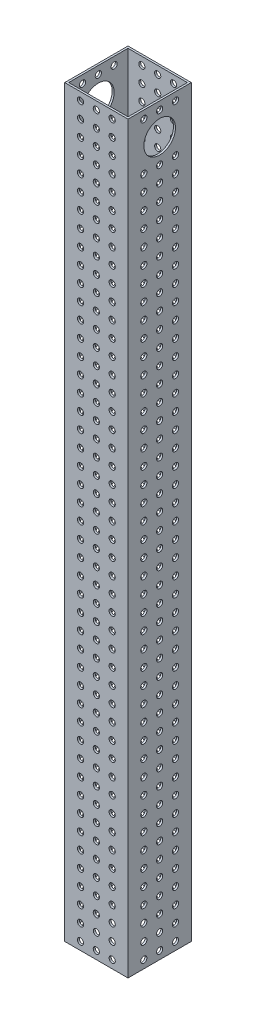
SolidWorks part; units mm, degrees
ref_plane "Front Plane" through (0, 0, 0) normal (0, 0, 1) x (1, 0, 0)
ref_plane "Top Plane" through (0, 0, 0) normal (0, 1, 0) x (1, 0, 0)
ref_plane "Right Plane" through (0, 0, 0) normal (1, 0, 0) x (0, 0, -1)
sketch "Sketch1" plane through (0, 0, 0) normal (0, 1, 0) x (1, 0, 0)
  line L1 (-25.4, 25.4) -> (25.4, 25.4)
  line L2 (-25.4, 25.4) -> (-25.4, -25.4)
  line L3 (-25.4, -25.4) -> (25.4, -25.4)
  line L4 (25.4, 25.4) -> (25.4, -25.4)
  line L5 (-25.4, 25.4) -> (25.4, -25.4) construction
  line L6 (-25.4, -25.4) -> (25.4, 25.4) construction
  line L7 (23.8125, 23.8125) -> (-23.8125, 23.8125)
  line L8 (23.8125, 23.8125) -> (23.8125, -23.8125)
  line L9 (23.8125, -23.8125) -> (-23.8125, -23.8125)
  line L10 (-23.8125, 23.8125) -> (-23.8125, -23.8125)
  line L11 (23.8125, 23.8125) -> (-23.8125, -23.8125) construction
  line L12 (23.8125, -23.8125) -> (-23.8125, 23.8125) construction
  point P0 (0, 0)
  point P6 (0, 0)
  dimension "D1" = 50.8
  dimension "D2" = 50.8
  dimension "D3" = 1.5875
  dimension "D4" = 1.5875
extrude "Boss-Extrude1" add sketch "Sketch1" along normal blind 685.8
sketch "Sketch2" plane through (0, 0, 25.4) normal (0, 0, 1) x (1, 0, 0)
  line L0 (0, 685.8) -> (0, 0) construction
  line L1 (-25.4, 685.8) -> (25.4, 685.8) construction
  line L2 (-25.4, 685.8) -> (-25.4, 0) construction
  line L3 (-6.35, 685.8) -> (-6.35, 0) construction
  line L5 (-25.4, 0) -> (25.4, 0) construction
  circle A0 centre (-12.7, 679.45) radius 2.4892
  circle A1 centre (-12.7, 666.75) radius 2.4892
  circle A2 centre (-12.7, 654.05) radius 2.4892
  circle A3 centre (-12.7, 641.35) radius 2.4892
  circle A4 centre (-12.7, 628.65) radius 2.4892
  circle A5 centre (-12.7, 615.95) radius 2.4892
  circle A6 centre (-12.7, 603.25) radius 2.4892
  circle A7 centre (-12.7, 590.55) radius 2.4892
  circle A8 centre (-12.7, 577.85) radius 2.4892
  circle A9 centre (-12.7, 565.15) radius 2.4892
  circle A10 centre (-12.7, 552.45) radius 2.4892
  circle A11 centre (-12.7, 539.75) radius 2.4892
  circle A12 centre (-12.7, 527.05) radius 2.4892
  circle A13 centre (-12.7, 514.35) radius 2.4892
  circle A14 centre (-12.7, 501.65) radius 2.4892
  circle A15 centre (-12.7, 488.95) radius 2.4892
  circle A16 centre (-12.7, 476.25) radius 2.4892
  circle A17 centre (-12.7, 463.55) radius 2.4892
  circle A18 centre (-12.7, 450.85) radius 2.4892
  circle A19 centre (-12.7, 438.15) radius 2.4892
  circle A20 centre (-12.7, 425.45) radius 2.4892
  circle A21 centre (-12.7, 412.75) radius 2.4892
  circle A22 centre (-12.7, 400.05) radius 2.4892
  circle A23 centre (-12.7, 387.35) radius 2.4892
  circle A24 centre (-12.7, 374.65) radius 2.4892
  circle A25 centre (-12.7, 361.95) radius 2.4892
  circle A26 centre (-12.7, 349.25) radius 2.4892
  circle A27 centre (-12.7, 336.55) radius 2.4892
  circle A28 centre (-12.7, 323.85) radius 2.4892
  circle A29 centre (-12.7, 311.15) radius 2.4892
  circle A30 centre (-12.7, 298.45) radius 2.4892
  circle A31 centre (-12.7, 285.75) radius 2.4892
  circle A32 centre (-12.7, 273.05) radius 2.4892
  circle A33 centre (-12.7, 260.35) radius 2.4892
  circle A34 centre (-12.7, 247.65) radius 2.4892
  circle A35 centre (-12.7, 234.95) radius 2.4892
  circle A36 centre (-12.7, 222.25) radius 2.4892
  circle A37 centre (-12.7, 209.55) radius 2.4892
  circle A38 centre (-12.7, 196.85) radius 2.4892
  circle A39 centre (-12.7, 184.15) radius 2.4892
  circle A40 centre (-12.7, 171.45) radius 2.4892
  circle A41 centre (-12.7, 158.75) radius 2.4892
  circle A42 centre (-12.7, 146.05) radius 2.4892
  circle A43 centre (-12.7, 133.35) radius 2.4892
  circle A44 centre (-12.7, 120.65) radius 2.4892
  circle A45 centre (-12.7, 107.95) radius 2.4892
  circle A46 centre (-12.7, 95.25) radius 2.4892
  circle A47 centre (-12.7, 82.55) radius 2.4892
  circle A48 centre (-12.7, 69.85) radius 2.4892
  circle A49 centre (-12.7, 57.15) radius 2.4892
  circle A50 centre (-12.7, 44.45) radius 2.4892
  circle A51 centre (-12.7, 31.75) radius 2.4892
  circle A52 centre (-12.7, 19.05) radius 2.4892
  circle A53 centre (-12.7, 6.35) radius 2.4892
  circle A54 centre (12.7, 6.35) radius 2.4892
  circle A55 centre (12.7, 19.05) radius 2.4892
  circle A56 centre (12.7, 31.75) radius 2.4892
  circle A57 centre (12.7, 44.45) radius 2.4892
  circle A58 centre (12.7, 57.15) radius 2.4892
  circle A59 centre (12.7, 69.85) radius 2.4892
  circle A60 centre (12.7, 82.55) radius 2.4892
  circle A61 centre (12.7, 95.25) radius 2.4892
  circle A62 centre (12.7, 107.95) radius 2.4892
  circle A63 centre (12.7, 120.65) radius 2.4892
  circle A64 centre (12.7, 133.35) radius 2.4892
  circle A65 centre (12.7, 146.05) radius 2.4892
  circle A66 centre (12.7, 158.75) radius 2.4892
  circle A67 centre (12.7, 171.45) radius 2.4892
  circle A68 centre (12.7, 184.15) radius 2.4892
  circle A69 centre (12.7, 196.85) radius 2.4892
  circle A70 centre (12.7, 209.55) radius 2.4892
  circle A71 centre (12.7, 222.25) radius 2.4892
  circle A72 centre (12.7, 234.95) radius 2.4892
  circle A73 centre (12.7, 247.65) radius 2.4892
  circle A74 centre (12.7, 260.35) radius 2.4892
  circle A75 centre (12.7, 273.05) radius 2.4892
  circle A76 centre (12.7, 285.75) radius 2.4892
  circle A77 centre (12.7, 298.45) radius 2.4892
  circle A78 centre (12.7, 311.15) radius 2.4892
  circle A79 centre (12.7, 323.85) radius 2.4892
  circle A80 centre (12.7, 336.55) radius 2.4892
  circle A81 centre (12.7, 374.65) radius 2.4892
  circle A82 centre (12.7, 361.95) radius 2.4892
  circle A83 centre (12.7, 349.25) radius 2.4892
  circle A84 centre (12.7, 387.35) radius 2.4892
  circle A85 centre (12.7, 400.05) radius 2.4892
  circle A86 centre (12.7, 412.75) radius 2.4892
  circle A87 centre (12.7, 425.45) radius 2.4892
  circle A88 centre (12.7, 438.15) radius 2.4892
  circle A89 centre (12.7, 450.85) radius 2.4892
  circle A90 centre (12.7, 463.55) radius 2.4892
  circle A91 centre (12.7, 476.25) radius 2.4892
  circle A92 centre (12.7, 488.95) radius 2.4892
  circle A93 centre (12.7, 501.65) radius 2.4892
  circle A94 centre (12.7, 514.35) radius 2.4892
  circle A95 centre (12.7, 527.05) radius 2.4892
  circle A96 centre (12.7, 539.75) radius 2.4892
  circle A97 centre (12.7, 552.45) radius 2.4892
  circle A98 centre (12.7, 565.15) radius 2.4892
  circle A99 centre (12.7, 577.85) radius 2.4892
  circle A100 centre (12.7, 590.55) radius 2.4892
  circle A101 centre (12.7, 603.25) radius 2.4892
  circle A102 centre (12.7, 615.95) radius 2.4892
  circle A103 centre (12.7, 628.65) radius 2.4892
  circle A104 centre (12.7, 641.35) radius 2.4892
  circle A105 centre (12.7, 654.05) radius 2.4892
  circle A106 centre (12.7, 666.75) radius 2.4892
  circle A107 centre (12.7, 679.45) radius 2.4892
  circle A108 centre (0, 6.35) radius 2.4892
  circle A109 centre (0, 19.05) radius 2.4892
  circle A110 centre (0, 31.75) radius 2.4892
  circle A111 centre (0, 44.45) radius 2.4892
  circle A112 centre (0, 57.15) radius 2.4892
  circle A113 centre (0, 69.85) radius 2.4892
  circle A114 centre (0, 82.55) radius 2.4892
  circle A115 centre (0, 95.25) radius 2.4892
  circle A116 centre (0, 107.95) radius 2.4892
  circle A117 centre (0, 120.65) radius 2.4892
  circle A118 centre (0, 133.35) radius 2.4892
  circle A119 centre (0, 146.05) radius 2.4892
  circle A120 centre (0, 158.75) radius 2.4892
  circle A121 centre (0, 171.45) radius 2.4892
  circle A122 centre (0, 184.15) radius 2.4892
  circle A123 centre (0, 196.85) radius 2.4892
  circle A124 centre (0, 209.55) radius 2.4892
  circle A125 centre (0, 222.25) radius 2.4892
  circle A126 centre (0, 234.95) radius 2.4892
  circle A127 centre (0, 247.65) radius 2.4892
  circle A128 centre (0, 260.35) radius 2.4892
  circle A129 centre (0, 273.05) radius 2.4892
  circle A130 centre (0, 285.75) radius 2.4892
  circle A131 centre (0, 298.45) radius 2.4892
  circle A132 centre (0, 311.15) radius 2.4892
  circle A133 centre (0, 323.85) radius 2.4892
  circle A134 centre (0, 336.55) radius 2.4892
  circle A135 centre (0, 349.25) radius 2.4892
  circle A136 centre (0, 361.95) radius 2.4892
  circle A137 centre (0, 374.65) radius 2.4892
  circle A138 centre (0, 387.35) radius 2.4892
  circle A139 centre (0, 400.05) radius 2.4892
  circle A140 centre (0, 412.75) radius 2.4892
  circle A141 centre (0, 425.45) radius 2.4892
  circle A142 centre (0, 438.15) radius 2.4892
  circle A143 centre (0, 450.85) radius 2.4892
  circle A144 centre (0, 463.55) radius 2.4892
  circle A145 centre (0, 476.25) radius 2.4892
  circle A146 centre (0, 488.95) radius 2.4892
  circle A147 centre (0, 501.65) radius 2.4892
  circle A148 centre (0, 514.35) radius 2.4892
  circle A149 centre (0, 527.05) radius 2.4892
  circle A150 centre (0, 539.75) radius 2.4892
  circle A151 centre (0, 552.45) radius 2.4892
  circle A152 centre (0, 565.15) radius 2.4892
  circle A153 centre (0, 577.85) radius 2.4892
  circle A154 centre (0, 590.55) radius 2.4892
  circle A155 centre (0, 603.25) radius 2.4892
  circle A156 centre (0, 615.95) radius 2.4892
  circle A157 centre (0, 628.65) radius 2.4892
  circle A158 centre (0, 641.35) radius 2.4892
  circle A159 centre (0, 654.05) radius 2.4892
  circle A160 centre (0, 666.75) radius 2.4892
  circle A161 centre (0, 679.45) radius 2.4892
  dimension "D1" = 4.9784
  dimension "D2" = 6.35
  dimension "D3" = 12.7
  dimension "D5" = 12.7
  dimension "D6" = 6.35
  dimension "D4" = 54
extrude "Cut-Extrude1" cut sketch "Sketch2" against normal through all
sketch "Sketch4" plane through (25.4, 0, 0) normal (1, 0, 0) x (0, 0, -1)
  line L0 (0, 685.8) -> (0, 0) construction
  line L1 (-25.4, 685.8) -> (25.4, 685.8) construction
  line L2 (-25.4, 685.8) -> (-25.4, 0) construction
  line L3 (-6.35, -314.2) -> (-6.35, 49685.8) construction
  line L4 (25.4, 584.2) -> (-25.4, 584.2) construction
  line L5 (25.4, 685.8) -> (25.4, 0) construction
  circle A0 centre (-12.7, 679.45) radius 2.4892
  circle A1 centre (-12.7, 666.75) radius 2.4892
  circle A2 centre (-12.7, 654.05) radius 2.4892
  circle A3 centre (-12.7, 641.35) radius 2.4892
  circle A4 centre (-12.7, 628.65) radius 2.4892
  circle A5 centre (-12.7, 615.95) radius 2.4892
  circle A6 centre (-12.7, 603.25) radius 2.4892
  circle A7 centre (-12.7, 590.55) radius 2.4892
  circle A10 centre (-12.7, 552.45) radius 2.4892
  circle A11 centre (-12.7, 539.75) radius 2.4892
  circle A12 centre (-12.7, 527.05) radius 2.4892
  circle A13 centre (-12.7, 514.35) radius 2.4892
  circle A14 centre (-12.7, 501.65) radius 2.4892
  circle A15 centre (-12.7, 488.95) radius 2.4892
  circle A16 centre (-12.7, 476.25) radius 2.4892
  circle A17 centre (-12.7, 463.55) radius 2.4892
  circle A18 centre (-12.7, 450.85) radius 2.4892
  circle A19 centre (-12.7, 438.15) radius 2.4892
  circle A20 centre (-12.7, 425.45) radius 2.4892
  circle A21 centre (-12.7, 412.75) radius 2.4892
  circle A22 centre (-12.7, 400.05) radius 2.4892
  circle A23 centre (-12.7, 387.35) radius 2.4892
  circle A24 centre (-12.7, 374.65) radius 2.4892
  circle A25 centre (-12.7, 361.95) radius 2.4892
  circle A26 centre (-12.7, 349.25) radius 2.4892
  circle A27 centre (-12.7, 336.55) radius 2.4892
  circle A28 centre (-12.7, 323.85) radius 2.4892
  circle A29 centre (-12.7, 311.15) radius 2.4892
  circle A30 centre (-12.7, 298.45) radius 2.4892
  circle A31 centre (-12.7, 285.75) radius 2.4892
  circle A32 centre (-12.7, 273.05) radius 2.4892
  circle A33 centre (-12.7, 260.35) radius 2.4892
  circle A34 centre (-12.7, 247.65) radius 2.4892
  circle A35 centre (-12.7, 234.95) radius 2.4892
  circle A36 centre (-12.7, 222.25) radius 2.4892
  circle A37 centre (-12.7, 209.55) radius 2.4892
  circle A38 centre (-12.7, 196.85) radius 2.4892
  circle A39 centre (-12.7, 184.15) radius 2.4892
  circle A40 centre (-12.7, 171.45) radius 2.4892
  circle A41 centre (-12.7, 158.75) radius 2.4892
  circle A42 centre (-12.7, 146.05) radius 2.4892
  circle A43 centre (-12.7, 133.35) radius 2.4892
  circle A44 centre (-12.7, 120.65) radius 2.4892
  circle A45 centre (-12.7, 107.95) radius 2.4892
  circle A46 centre (-12.7, 95.25) radius 2.4892
  circle A47 centre (-12.7, 82.55) radius 2.4892
  circle A48 centre (-12.7, 69.85) radius 2.4892
  circle A49 centre (-12.7, 57.15) radius 2.4892
  circle A50 centre (-12.7, 44.45) radius 2.4892
  circle A51 centre (-12.7, 31.75) radius 2.4892
  circle A52 centre (-12.7, 19.05) radius 2.4892
  circle A53 centre (-12.7, 6.35) radius 2.4892
  circle A54 centre (12.7, 273.05) radius 2.4892
  circle A55 centre (12.7, 285.75) radius 2.4892
  circle A56 centre (12.7, 298.45) radius 2.4892
  circle A57 centre (12.7, 311.15) radius 2.4892
  circle A58 centre (12.7, 323.85) radius 2.4892
  circle A59 centre (12.7, 336.55) radius 2.4892
  circle A60 centre (12.7, 349.25) radius 2.4892
  circle A61 centre (12.7, 361.95) radius 2.4892
  circle A62 centre (12.7, 374.65) radius 2.4892
  circle A63 centre (12.7, 387.35) radius 2.4892
  circle A64 centre (12.7, 400.05) radius 2.4892
  circle A65 centre (12.7, 412.75) radius 2.4892
  circle A66 centre (12.7, 425.45) radius 2.4892
  circle A67 centre (12.7, 438.15) radius 2.4892
  circle A68 centre (12.7, 450.85) radius 2.4892
  circle A69 centre (12.7, 463.55) radius 2.4892
  circle A70 centre (12.7, 476.25) radius 2.4892
  circle A71 centre (12.7, 488.95) radius 2.4892
  circle A72 centre (12.7, 501.65) radius 2.4892
  circle A73 centre (12.7, 514.35) radius 2.4892
  circle A74 centre (12.7, 527.05) radius 2.4892
  circle A75 centre (12.7, 539.75) radius 2.4892
  circle A76 centre (12.7, 552.45) radius 2.4892
  circle A79 centre (12.7, 590.55) radius 2.4892
  circle A80 centre (12.7, 603.25) radius 2.4892
  circle A81 centre (12.7, 615.95) radius 2.4892
  circle A82 centre (12.7, 628.65) radius 2.4892
  circle A83 centre (12.7, 641.35) radius 2.4892
  circle A84 centre (12.7, 654.05) radius 2.4892
  circle A85 centre (12.7, 666.75) radius 2.4892
  circle A86 centre (12.7, 19.05) radius 2.4892
  circle A87 centre (12.7, 31.75) radius 2.4892
  circle A88 centre (12.7, 44.45) radius 2.4892
  circle A89 centre (12.7, 57.15) radius 2.4892
  circle A90 centre (12.7, 69.85) radius 2.4892
  circle A91 centre (12.7, 82.55) radius 2.4892
  circle A92 centre (12.7, 95.25) radius 2.4892
  circle A93 centre (12.7, 107.95) radius 2.4892
  circle A94 centre (12.7, 120.65) radius 2.4892
  circle A95 centre (12.7, 133.35) radius 2.4892
  circle A96 centre (12.7, 146.05) radius 2.4892
  circle A97 centre (12.7, 158.75) radius 2.4892
  circle A98 centre (12.7, 171.45) radius 2.4892
  circle A99 centre (12.7, 184.15) radius 2.4892
  circle A100 centre (12.7, 196.85) radius 2.4892
  circle A101 centre (12.7, 209.55) radius 2.4892
  circle A102 centre (12.7, 222.25) radius 2.4892
  circle A103 centre (12.7, 234.95) radius 2.4892
  circle A104 centre (12.7, 247.65) radius 2.4892
  circle A105 centre (12.7, 260.35) radius 2.4892
  circle A106 centre (12.7, 6.35) radius 2.4892
  circle A107 centre (12.7, 679.45) radius 2.4892
  circle A108 centre (0, 6.35) radius 2.4892
  circle A109 centre (0, 19.05) radius 2.4892
  circle A110 centre (0, 31.75) radius 2.4892
  circle A111 centre (0, 44.45) radius 2.4892
  circle A112 centre (0, 57.15) radius 2.4892
  circle A113 centre (0, 69.85) radius 2.4892
  circle A114 centre (0, 82.55) radius 2.4892
  circle A115 centre (0, 95.25) radius 2.4892
  circle A116 centre (0, 107.95) radius 2.4892
  circle A117 centre (0, 120.65) radius 2.4892
  circle A118 centre (0, 133.35) radius 2.4892
  circle A119 centre (0, 146.05) radius 2.4892
  circle A120 centre (0, 158.75) radius 2.4892
  circle A121 centre (0, 171.45) radius 2.4892
  circle A122 centre (0, 184.15) radius 2.4892
  circle A123 centre (0, 196.85) radius 2.4892
  circle A124 centre (0, 209.55) radius 2.4892
  circle A125 centre (0, 222.25) radius 2.4892
  circle A126 centre (0, 234.95) radius 2.4892
  circle A127 centre (0, 247.65) radius 2.4892
  circle A128 centre (0, 260.35) radius 2.4892
  circle A129 centre (0, 273.05) radius 2.4892
  circle A130 centre (0, 285.75) radius 2.4892
  circle A131 centre (0, 298.45) radius 2.4892
  circle A132 centre (0, 311.15) radius 2.4892
  circle A133 centre (0, 323.85) radius 2.4892
  circle A134 centre (0, 336.55) radius 2.4892
  circle A135 centre (0, 349.25) radius 2.4892
  circle A136 centre (0, 361.95) radius 2.4892
  circle A137 centre (0, 374.65) radius 2.4892
  circle A138 centre (0, 387.35) radius 2.4892
  circle A139 centre (0, 400.05) radius 2.4892
  circle A140 centre (0, 412.75) radius 2.4892
  circle A141 centre (0, 425.45) radius 2.4892
  circle A142 centre (0, 438.15) radius 2.4892
  circle A143 centre (0, 450.85) radius 2.4892
  circle A144 centre (0, 463.55) radius 2.4892
  circle A145 centre (0, 476.25) radius 2.4892
  circle A146 centre (0, 488.95) radius 2.4892
  circle A147 centre (0, 501.65) radius 2.4892
  circle A148 centre (0, 514.35) radius 2.4892
  circle A149 centre (0, 527.05) radius 2.4892
  circle A150 centre (0, 539.75) radius 2.4892
  circle A151 centre (0, 552.45) radius 2.4892
  circle A154 centre (0, 590.55) radius 2.4892
  circle A155 centre (0, 603.25) radius 2.4892
  circle A156 centre (0, 615.95) radius 2.4892
  circle A157 centre (0, 628.65) radius 2.4892
  circle A158 centre (0, 641.35) radius 2.4892
  circle A159 centre (0, 654.05) radius 2.4892
  circle A160 centre (0, 666.75) radius 2.4892
  circle A161 centre (0, 679.45) radius 2.4892
  circle A162 centre (-12.7, 565.15) radius 2.4892 [skipped]
  circle A163 centre (-12.7, 577.85) radius 2.4892 [skipped]
  dimension "D1" = 4.9784
  dimension "D2" = 12.7
  dimension "D3" = 6.35
  dimension "D5" = 12.7
  dimension "D6" = 6.35
  dimension "D7" = 101.6
  dimension "D4" = 54
extrude "Cut-Extrude2" cut sketch "Sketch4" against normal through all
sketch "Sketch5" plane through (25.4, 0, 0) normal (1, 0, 0) x (0, 0, -1)
  line L0 (25.4, 685.8) -> (25.4, 0) construction
  line L1 (25.4, 609.6) -> (-25.4, 609.6)
  line L6 (-25.4, 685.8) -> (25.4, 685.8)
  line L7 (-25.4, 685.8) -> (-25.4, 609.6)
  line L8 (-25.4, 609.6) -> (25.4, 609.6)
  line L9 (25.4, 685.8) -> (25.4, 609.6)
  dimension "D1" = 50.8
  dimension "D2" = 76.2
  dimension "D3" = 76.2
extrude "Cut-Extrude3" cut sketch "Sketch5" against normal through all contours L9 L6 L7 L1 region at (25.4, 647.7, 0)
sketch "Sketch6" plane through (25.4, 0, 0) normal (1, 0, 0) x (0, 0, -1)
  line L0 (0, 609.6) -> (0, 0) construction
  line L1 (25.4, 609.6) -> (-25.4, 609.6) construction
  circle A0 centre (0, 571.9064) radius 12.7
  dimension "D2" = 25.4
  dimension "D1" = 37.6936
extrude "Cut-Extrude4" cut sketch "Sketch6" against normal through all
sketch "Sketch7" plane through (25.4, 0, 0) normal (1, 0, 0) x (0, 0, -1)
  line L0 (28.8601, 596.9) -> (-12.7, 596.9) construction
  line L1 (28.8601, 596.9) -> (-12.7, 596.9)
  line L2 (-12.7, 596.9) -> (-25.4, 596.9)
  line L3 (-25.4, 596.9) -> (-25.4, 609.6)
  line L4 (-25.4, 609.6) -> (25.4, 609.6)
  line L5 (25.4, 609.6) -> (25.4, 596.9)
  line L6 (-25.4, 609.6) -> (-25.4, 0) construction
  line L7 (25.4, 609.6) -> (-25.4, 609.6) construction
extrude "Cut-Extrude5" cut sketch "Sketch7" against normal through all contours L5 L4 L3 L2 L1 region at (25.4, 603.25, 0)
